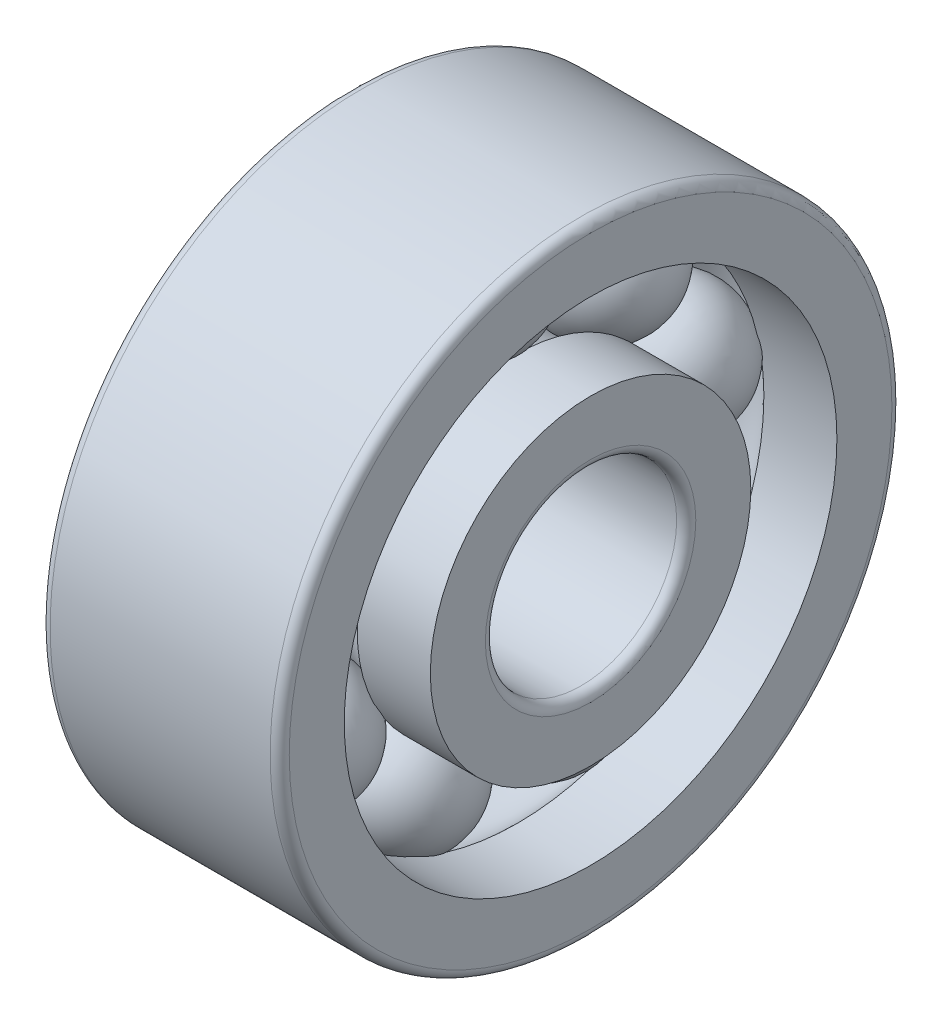
SolidWorks part; units mm, degrees
ref_plane "Plane1" through (0, 0, 0) normal (0, 0, 1) x (1, 0, 0)
ref_plane "Plane2" through (0, 0, 0) normal (0, 1, 0) x (1, 0, 0)
ref_plane "Plane3" through (0, 0, 0) normal (1, 0, 0) x (0, 0, -1)
other "Configuration Table"
sketch "Clipboard" plane through (0, 0, 0) normal (0, 0, 1) x (1, 0, 0)
  line L0 (-10, 0) -> (10, 0) construction
  line L1 (0, 0) -> (22.0854, -3.498)
  line L2 (0, 0) -> (4.2494, -0.0742)
  line L3 (0, 0) -> (22.3573, 0.3902)
  line L4 (0, 0) -> (-22.3573, -0.3902)
  dimension "BallCLRad" = 4.25
sketch "CagSpiSke" plane through (0, 0, 0) normal (0, 0, 1) x (1, 0, 0)
  line L0 (0.135, 4.025) -> (0.135, 4.475)
  line L1 (0.135, 4.475) -> (-0.135, 4.475)
  line L2 (-0.135, 4.475) -> (-0.135, 4.025)
  line L3 (-0.135, 4.025) -> (0.135, 4.025)
  line L4 (-20.6375, 0) -> (20.6375, 0) construction
  line L5 (0, 0) -> (0, 23.7692) construction
  dimension "OD" = 8.95
  dimension "ID" = 8.05
revolve "CageSpine" add sketch "CagSpiSke" angle 0.001 about L4
ref_axis "Axis1" through (-50, 0, 0) along (1, 0, 0)
sketch "CagBalSke" plane through (0, 0, 0) normal (0, 0, 1) x (1, 0, 0)
  line L0 (-1.485, 4.25) -> (1.485, 4.25)
  line L1 (-1.905, 4.25) -> (1.905, 4.25) construction
  line L2 (-10, 0) -> (10, 0) construction
  line L3 (0, 0) -> (0, 24) construction
  arc A0 (1.485, 4.25) -> (-1.485, 4.25) centre (0, 4.25) cw
  dimension "BallCLRad" = 4.25
revolve "CageBall" [suppressed] add sketch "CagBalSke" angle 360 about L1 reverse direction yes
pattern_circular "CageBalls" [suppressed] count 9 every 40 about axis through (-50, 0, 0) along (1, 0, 0)
sketch "CagTrmODSke" plane through (0, 0, 0) normal (0, 0, 1) x (1, 0, 0)
  line L0 (1.486, 4.475) -> (1.486, 5.736)
  line L1 (1.486, 5.736) -> (-1.486, 5.736)
  line L2 (-1.486, 5.736) -> (-1.486, 4.475)
  line L3 (-1.486, 4.475) -> (1.486, 4.475)
  line L4 (-20.6375, 0) -> (20.6375, 0) construction
  line L5 (0, 0) -> (0, 25) construction
  dimension "Width" = 2.972
  dimension "ID" = 8.95
  dimension "OD" = 11.472
revolve "CageTrimOD" [suppressed] cut sketch "CagTrmODSke" angle 360 about L4 reverse direction yes
sketch "CagTrmIDSke" plane through (0, 0, 0) normal (0, 0, 1) x (1, 0, 0)
  line L0 (1.486, 2.766) -> (1.486, 4.025)
  line L1 (1.486, 4.025) -> (-1.486, 4.025)
  line L2 (-1.486, 4.025) -> (-1.486, 2.766)
  line L3 (-1.486, 2.766) -> (1.486, 2.766)
  line L4 (-20.6375, 0) -> (20.6375, 0) construction
  line L5 (0, 0) -> (0, 25) construction
  dimension "Width" = 2.972
  dimension "ID" = 5.532
  dimension "OD" = 8.05
revolve "CageTrimID" [suppressed] cut sketch "CagTrmIDSke" angle 360 about L4 reverse direction yes
sketch "BalSimSke" plane through (0, 0, 0) normal (0, 0, 1) x (1, 0, 0)
  line L0 (-10, 0) -> (10, 0) construction
  line L1 (-10, 4.25) -> (10, 4.25) construction
  line L2 (0, 0) -> (0, 23) construction
  circle A0 centre (0, 4.25) radius 1.35
  dimension "BallCLRad" = 4.25
  dimension "Ball_diameter" = 2.7
revolve "BallsSimplified" [suppressed] add sketch "BalSimSke" angle 360 about L0
sketch "BalDetSke" plane through (0, 0, 0) normal (0, 0, 1) x (1, 0, 0)
  line L0 (-1.35, 4.25) -> (1.35, 4.25)
  line L1 (-1.905, 4.25) -> (1.905, 4.25) construction
  line L2 (0, 0) -> (0, 25) construction
  arc A0 (1.35, 4.25) -> (-1.35, 4.25) centre (0, 4.25) cw
  dimension "BallCLRad" = 4.25
  dimension "Ball_diameter" = 2.7
revolve "BallDetailed" add sketch "BalDetSke" angle 360 about L1 reverse direction yes
sketch "InnRacSke" plane through (0, 0, 0) normal (0, 0, 1) x (1, 0, 0)
  line L0 (-0.9724, 3.35) -> (-2.5, 3.35)
  line L1 (-2.5, 3.35) -> (-2.5, 2.2)
  line L2 (-2.3, 2) -> (2.3, 2)
  line L3 (2.5, 2.2) -> (2.5, 3.35)
  line L4 (2.5, 3.35) -> (0.9724, 3.35)
  line L5 (-20.6375, 0) -> (20.6375, 0) construction
  line L6 (0, 0) -> (0, 30) construction
  arc A0 (-2.5, 2.2) -> (-2.3, 2) centre (-2.3, 2.2) ccw
  arc A1 (2.3, 2) -> (2.5, 2.2) centre (2.3, 2.2) ccw
  arc A2 (0.9724, 3.35) -> (-0.9724, 3.35) centre (0, 4.25) cw
  dimension "BallCLRad" = 4.25
  dimension "Fillet_radius" = 0.2
  dimension "Ball_diameter" = 2.65
  dimension "ID" = 4
  dimension "OD" = 6.7
  dimension "Width" = 5
revolve "InnerRace" add sketch "InnRacSke" angle 360 about L5 reverse direction yes
sketch "OutRacSke" plane through (0, 0, 0) normal (0, 0, 1) x (1, 0, 0)
  line L0 (-0.9724, 5.15) -> (-2.5, 5.15)
  line L1 (-2.5, 5.15) -> (-2.5, 6.3)
  line L2 (-2.3, 6.5) -> (2.3, 6.5)
  line L3 (2.5, 6.3) -> (2.5, 5.15)
  line L4 (2.5, 5.15) -> (0.9724, 5.15)
  line L5 (-20.6375, 0) -> (20.6375, 0) construction
  line L6 (0, 0) -> (0, 30) construction
  arc A0 (-2.5, 6.3) -> (-2.3, 6.5) centre (-2.3, 6.3) cw
  arc A1 (2.3, 6.5) -> (2.5, 6.3) centre (2.3, 6.3) cw
  arc A2 (0.9724, 5.15) -> (-0.9724, 5.15) centre (0, 4.25) ccw
  dimension "BallCLRad" = 4.25
  dimension "Fillet_radius" = 0.2
  dimension "Ball_diameter" = 2.65
  dimension "Width" = 5
revolve "OuterRace" add sketch "OutRacSke" angle 360 about L5 reverse direction yes
pattern_circular "BallsDetailed" count 9 every 40 about axis through (-50, 0, 0) along (1, 0, 0) of "BallDetailed"
equation "\"BallCLRad@Clipboard\" = ( \"OD@OutRacSke\" + \"ID@InnRacSke\" ) / 4"
equation "\"BallCLRad@BalSimSke\" = \"BallCLRad@Clipboard\""
equation "\"BallCLRad@BalDetSke\" = \"BallCLRad@Clipboard\""
equation "\"BallCLRad@InnRacSke\" = \"BallCLRad@Clipboard\""
equation "\"BallCLRad@OutRacSke\" = \"BallCLRad@Clipboard\""
equation "\"Ball_diameter@InnRacSke\" = \"Ball_diameter@BalDetSke\" - 0.05"
equation "\"Ball_diameter@OutRacSke\" = \"Ball_diameter@BalDetSke\" - 0.05"
equation "\"Ball_diameter@BalSimSke\" = \"Ball_diameter@BalDetSke\""
equation "\"Width@OutRacSke\" = \"Width@InnRacSke\""
equation "\"Fillet_radius@OutRacSke\" = \"Fillet_radius@InnRacSke\""
equation "\"Max_count@Clipboard\" = int( 3.14159265 / atn(( \"Ball_diameter@BalDetSke\" / 2) / sqr( \"BallCLRad@Clipboard\"  *  \"BallCLRad@Clipboard\" - ( \"Ball_diameter@BalDetSke\" / 2) *  ( \"Ball_diameter@BalDetSke\" / 2))))"
equation "\"Max_count@Clipboard\" = ((sgn( \"Max_count@Clipboard\" - \"Count@Clipboard\" )-1)*( \"Max_count@Clipboard\" - \"Count@Clipboard\" ))/-2+ \"Count@Clipboard\""
equation "\"Count@BallsDetailed\" = int( \"Show_count@Clipboard\" ) "
equation "\"Count@BallsDetailed\" = ((sgn( \"Count@BallsDetailed\" - \"Max_count@Clipboard\" )-1)*( \"Count@BallsDetailed\" - \"Max_count@Clipboard\" ))/-2+ \"Max_count@Clipboard\""
equation "\"Count@BallsDetailed\" = ((sgn( \"Count@BallsDetailed\" - \"Min_count@Clipboard\" )+1)*( \"Count@BallsDetailed\" - \"Min_count@Clipboard\"))/2 +\"Min_count@Clipboard\""
equation "\"Angle@BallsDetailed\" = 360.0 / \"Max_count@Clipboard\""
equation "\"BallCLRad@CagBalSke\" = \"BallCLRad@Clipboard\""
equation "\"Count@CageBalls\" = \"Count@BallsDetailed\""
equation "\"Angle@CageBalls\" = \"Angle@BallsDetailed\""
equation "\"Angle@CageSpine\" =  \"Angle@CageBalls\" * ( \"Count@CageBalls\" -1 + int( \"Count@CageBalls\" / \"Max_count@Clipboard\" ) )  + 0.001 -  int( \"Count@CageBalls\" / \"Max_count@Clipboard\" ) * 0.001"
equation "\"Angle@CageSpine\" =  \"Angle@CageSpine\" * int( \"Min_count@Clipboard\" / 2) + int(1 / \"Min_count@Clipboard\")  * 0.001"
equation "\"CageWallOD@CagBalSke\" =  \"Ball_diameter@BalDetSke\" * 1.1"
equation "\"Thickness@CagSpiSke\" =  \"Ball_diameter@BalDetSke\" * 0.1"
equation "\"OD@CagTrmODSke\" = \"BallCLRad@Clipboard\" * 2 + \"CageWallOD@CagBalSke\" + 0.002"
equation "\"ID@CagTrmODSke\" = \"BallCLRad@Clipboard\" * 2 + \"Ball_diameter@BalDetSke\" / 6"
equation "\"OD@CagTrmIDSke\" = \"BallCLRad@Clipboard\" * 2 - \"Ball_diameter@BalDetSke\" / 6"
equation "\"ID@CagTrmIDSke\" = \"BallCLRad@Clipboard\" * 2 - \"CageWallOD@CagBalSke\" + 0.002"
equation "\"OD@CagSpiSke\" = \"ID@CagTrmODSke\""
equation "\"ID@CagSpiSke\" = \"OD@CagTrmIDSke\""
equation "\"Width@CagTrmODSke\" = \"CageWallOD@CagBalSke\" + 0.002"
equation "\"Width@CagTrmIDSke\" = \"CageWallOD@CagBalSke\" + 0.002"
